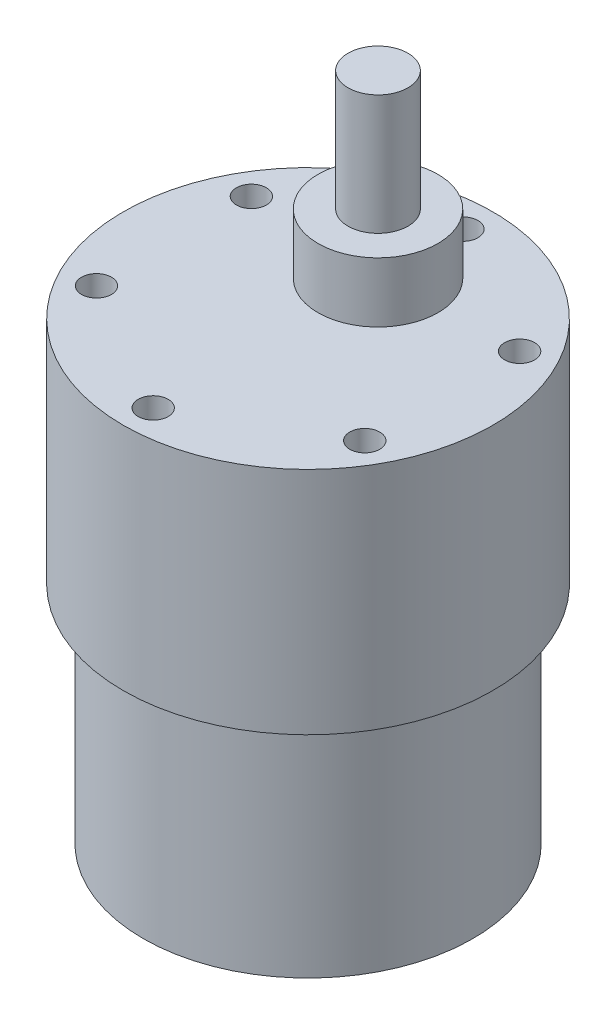
SolidWorks part; units mm, degrees
ref_plane "前视基准面" through (0, 0, 0) normal (0, 0, 1) x (1, 0, 0)
ref_plane "上视基准面" through (0, 0, 0) normal (0, 1, 0) x (1, 0, 0)
ref_plane "右视基准面" through (0, 0, 0) normal (1, 0, 0) x (0, 0, -1)
sketch "草图1" plane through (0, 0, 0) normal (0, 1, 0) x (1, 0, 0)
  circle A0 centre (0, 0) radius 18.5
  dimension "D1" = 37
extrude "凸台-拉伸1" add sketch "草图1" against normal blind 23
sketch "草图3" plane through (0, -23, 0) normal (0, -1, 0) x (1, 0, 0)
  circle A0 centre (0, 0) radius 16.5
  dimension "D1" = 33
extrude "凸台-拉伸2" add sketch "草图3" along normal blind 22.5
sketch "草图4" plane through (0, 0, 0) normal (0, 1, 0) x (1, 0, 0)
  circle A0 centre (0, 0) radius 15.5 construction
  circle A1 centre (0, 15.5) radius 1.5
  circle A2 centre (13.4234, 7.75) radius 1.5
  circle A3 centre (13.4234, -7.75) radius 1.5
  circle A4 centre (0, -15.5) radius 1.5
  circle A5 centre (-13.4234, -7.75) radius 1.5
  circle A6 centre (-13.4234, 7.75) radius 1.5
  point P17 (0, 0)
  dimension "D1" = 31
  dimension "D2" = 3
  dimension "D3" = 6
extrude "切除-拉伸1" cut sketch "草图4" against normal blind 15
sketch "草图5" plane through (0, 0, 0) normal (0, 1, 0) x (1, 0, 0)
  circle A0 centre (0, 7) radius 6
  dimension "D1" = 12
  dimension "D2" = 7
extrude "凸台-拉伸3" add sketch "草图5" along normal blind 6
sketch "草图6" plane through (0, 6, 0) normal (0, 1, 0) x (1, 0, 0)
  circle A0 centre (0, 7) radius 3
  circle A1 centre (0, 7) radius 6 construction
  dimension "D1" = 6
extrude "凸台-拉伸4" add sketch "草图6" along normal blind 12
sketch "草图7" plane through (0, -45.5, 0) normal (0, -1, 0) x (1, 0, 0)
  circle A0 centre (0, 0) radius 7
  dimension "D1" = 14
extrude "凸台-拉伸5" add sketch "草图7" along normal blind 6.2
